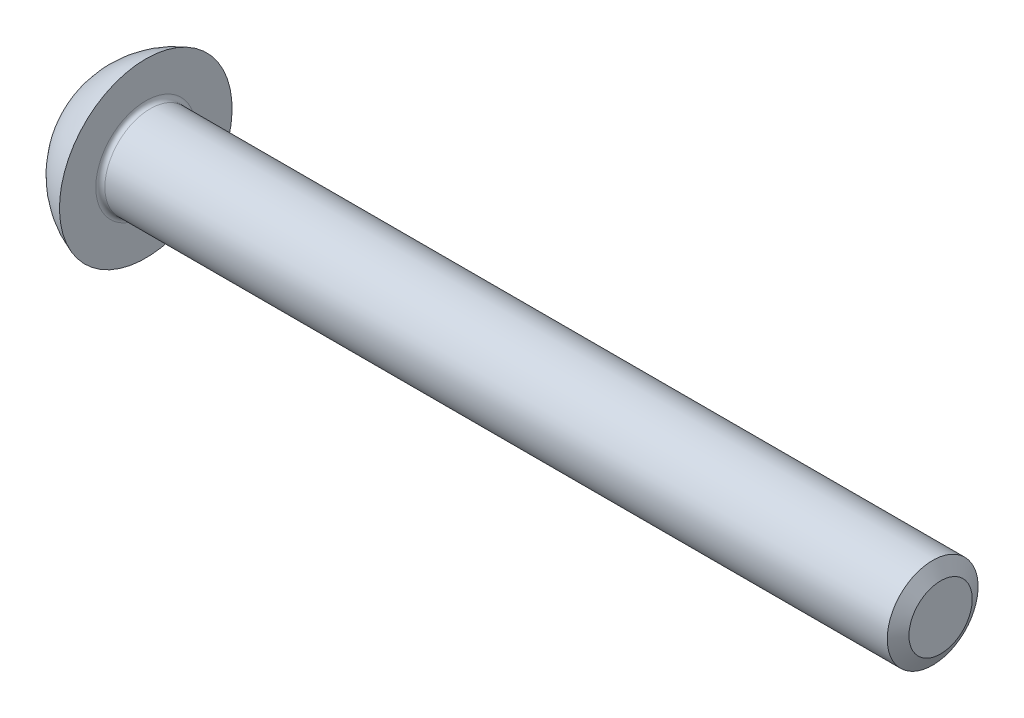
SolidWorks part; units mm, degrees
ref_plane "前视基准面" through (0, 0, 0) normal (0, 0, 1) x (1, 0, 0)
ref_plane "上视基准面" through (0, 0, 0) normal (0, 1, 0) x (1, 0, 0)
ref_plane "右视基准面" through (0, 0, 0) normal (1, 0, 0) x (0, 0, -1)
sketch "尺寸草图" plane through (0, 0, 0) normal (0, 0, 1) x (1, 0, 0)
  line L0 (0, 0) -> (35, 0) construction
  line L1 (35, 0) -> (35, 2) construction
  line L2 (35, 2) -> (34.3, 2) construction
  line L3 (0, 0) -> (0, 3.8) construction
  point P3 (1.4, 0)
  point P6 (35, 2.35)
  point P7 (0, 0.93)
  point P9 (2.2, 0)
  point P10 (2.4, 0)
  point P11 (35, 1.25)
  point P12 (3.7, 0)
  point P13 (4, 0)
  point P14 (35, 22.35)
  dimension "l" = 35
  dimension "d" = 4
  dimension "P" = 0.7
  dimension "a" = 1.4
  dimension "da" = 4.7
  dimension "dk" = 7.6
  dimension "e" = 2.87
  dimension "K" = 2.2
  dimension "r" = 0.2
  dimension "s" = 2.5
  dimension "t" = 1.3
  dimension "w" = 0.3
  dimension "zslwx" = 20
sketch "草图1" plane through (0, 0, 0) normal (0, 0, 1) x (1, 0, 0)
  line L0 (-37.2, 0) -> (0, 0) construction
  line L1 (0, 2) -> (-34.8, 2)
  line L2 (-35, 2.2) -> (-35, 3.8)
  line L3 (-37.2, 0) -> (-37.2, 2)
  line L4 (0, 2) -> (0, 0)
  line L5 (-37.2, 0) -> (0, 0)
  arc A0 (-35, 3.8) -> (-37.2, 2) centre (-33.7273, 0) ccw
  arc A1 (-34.8, 2) -> (-35, 2.2) centre (-34.8, 2.2) cw
  point P10 (-35, 2)
  dimension "r" = 0.2
  dimension "d" = 4
  dimension "dk" = 7.6
  dimension "k" = 2.2
  dimension "l" = 35
revolve "旋转1" add sketch "草图1" angle 360 about L0
cosmetic thread "装饰螺纹线1" parameters "D1"=20, "D2"=3.44
sketch "草图2" plane through (-37.2, 0, 0) normal (-1, 0, 0) x (0, 0, 1)
  line L1 (0, 1.4434) -> (-1.25, 0.7217)
  line L2 (-1.25, 0.7217) -> (-1.25, -0.7217)
  line L3 (-1.25, -0.7217) -> (0, -1.4434)
  line L4 (0, -1.4434) -> (1.25, -0.7217)
  line L5 (1.25, -0.7217) -> (1.25, 0.7217)
  line L6 (1.25, 0.7217) -> (0, 1.4434)
  circle A0 centre (0, 0) radius 1.25 construction
  dimension "s" = 2.5
extrude "切除-拉伸1" cut sketch "草图2" against normal blind 2.2
sketch "草图6" plane through (0, 0, 0) normal (0, 0, 1) x (1, 0, 0)
  line L0 (-35.9, 1.4434) -> (-35, 0)
  line L1 (-34.63, 1.4434) -> (-34.63, 0)
  line L2 (-34.63, 1.4434) -> (-35.9, 1.4434)
  line L3 (-37.2, 0) -> (-35, 0) construction
  line L4 (-34.63, 0) -> (-35, 0)
  line L5 (-37.2, 0) -> (-40.07, 0) construction
  dimension "t" = 1.3
  dimension "e-s" = 0.37
  dimension "k" = 2.2
  dimension "e" = 2.87
revolve "旋转2" add sketch "草图6" angle 360 about L3
sketch "草图7" plane through (0, 0, 0) normal (0, 0, 1) x (1, 0, 0)
  line L3 (-37.2, 1.4434) -> (-36.83, 0)
  line L4 (-37.2, 0) -> (-36.83, 0) construction
  line L7 (-37.2, 1.4434) -> (-37.2, 0)
  line L8 (-37.2, 0) -> (-36.83, 0)
  dimension "e-s" = 0.37
revolve "切除-旋转5" cut sketch "草图7" angle 360 about L4
sketch "草图4" plane through (0, 0, 0) normal (0, 0, 1) x (1, 0, 0)
  line L0 (-0.35, 2) -> (0, 1.3938)
  line L1 (-0.35, 2) -> (0.35, 2)
  line L2 (0.35, 2) -> (0, 1.3938)
  line L4 (0, -2) -> (0, 2) construction
  line L5 (-0.35, 0) -> (0.35, 0) construction
  dimension "d" = 2
  dimension "p" = 0.7
revolve "切除-旋转1" cut sketch "草图4" angle 360 about L5
ref_axis "基准轴1" through (-8.1887, 0, 0) along (1, 0, 0)
pattern_linear "阵列(线性)1" [suppressed] count 48 spacing 0.7 along (-1, 0, 0) of bodies 104
